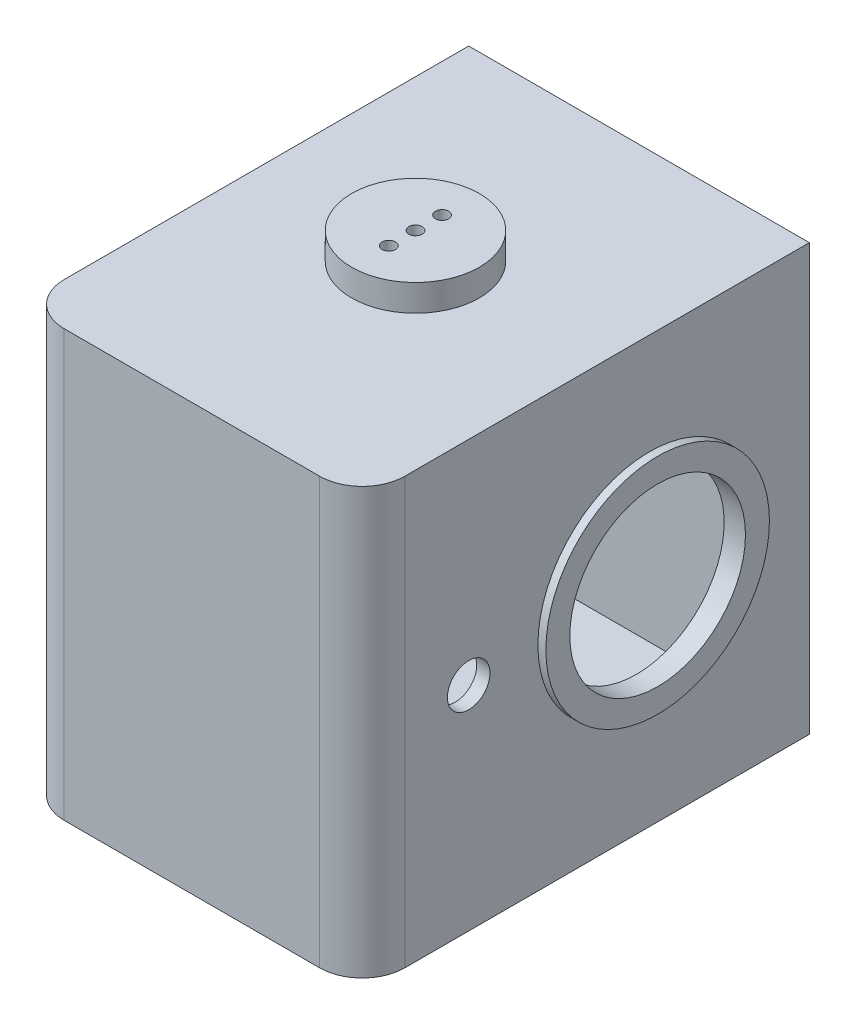
SolidWorks part; units mm, degrees
ref_plane "Front Plane" through (0, 0, 0) normal (0, 0, 1) x (1, 0, 0)
ref_plane "Top Plane" through (0, 0, 0) normal (0, 1, 0) x (1, 0, 0)
ref_plane "Right Plane" through (0, 0, 0) normal (1, 0, 0) x (0, 0, -1)
sketch "S_box1" plane through (0, 0, 0) normal (0, 0, 1) x (1, 0, 0)
  line L0 (-32, -40) -> (32, -40)
  line L1 (32, -40) -> (32, 40)
  line L2 (32, 40) -> (-32, 40)
  line L3 (-32, 40) -> (-32, -40)
  dimension "P1" = 32
  dimension "P2" = 40
  dimension "P3" = 32
  dimension "P4" = 40
  dimension "P5" = 32
  dimension "P6" = 40
  dimension "P7" = 32
  dimension "P8" = 40
extrude "Boss_1" add sketch "S_box1" along normal blind 76
ref_plane "PZ_p75_900" through (0, 0, 75.9) normal (0, 0, 1) x (1, 0, 0)
sketch "S_box2" plane through (0, 0, 75.9) normal (0, 0, 1) x (1, 0, 0)
  line L0 (-24, -40) -> (24, -40)
  line L1 (24, -40) -> (24, 40)
  line L2 (24, 40) -> (-24, 40)
  line L3 (-24, 40) -> (-24, -40)
  dimension "P1" = 24
  dimension "P2" = 40
  dimension "P3" = 24
  dimension "P4" = 40
  dimension "P5" = 24
  dimension "P6" = 40
  dimension "P7" = 24
  dimension "P8" = 40
extrude "Boss_2" add sketch "S_box2" along normal blind 8.1
ref_plane "PY_m40_000" through (0, -40, 0) normal (0, 1, 0) x (1, 0, 0)
sketch "S_cyl3" plane through (0, -40, 0) normal (0, 1, 0) x (1, 0, 0)
  circle A0 centre (-24, -76) radius 8
  dimension "D1_S_cyl3" = 16
  dimension "P2" = 24
  dimension "P3" = 76
extrude "Boss_3" add sketch "S_cyl3" along normal blind 80
sketch "S_cyl4" plane through (0, -40, 0) normal (0, 1, 0) x (1, 0, 0)
  circle A0 centre (24, -76) radius 8
  dimension "D1_S_cyl4" = 16
  dimension "P2" = 24
  dimension "P3" = 76
extrude "Boss_4" add sketch "S_cyl4" along normal blind 80
ref_plane "PX_p31_900" through (31.9, 0, 0) normal (1, 0, 0) x (0, 0, -1)
sketch "S_cyl5" plane through (31.9, 0, 0) normal (1, 0, 0) x (0, 0, -1)
  circle A0 centre (-30, 0) radius 21
  dimension "D1_S_cyl5" = 42
  dimension "P2" = 30
extrude "Boss_5" add sketch "S_cyl5" along normal blind 1.6
ref_plane "PY_p39_900" through (0, 39.9, 0) normal (0, 1, 0) x (1, 0, 0)
sketch "S_cyl6" plane through (0, 39.9, 0) normal (0, 1, 0) x (1, 0, 0)
  circle A0 centre (-2, -40) radius 12
  dimension "D1_S_cyl6" = 24
  dimension "P2" = 2
  dimension "P3" = 40
extrude "Boss_6" add sketch "S_cyl6" along normal blind 5.1
ref_plane "PY_m45_000" through (0, -45, 0) normal (0, 1, 0) x (1, 0, 0)
sketch "S_cyl7" plane through (0, -45, 0) normal (0, 1, 0) x (1, 0, 0)
  circle A0 centre (-2, -40) radius 12
  dimension "D1_S_cyl7" = 24
  dimension "P2" = 2
  dimension "P3" = 40
extrude "Boss_7" add sketch "S_cyl7" along normal blind 5.1
ref_plane "PZ_p2_500" through (0, 0, 2.5) normal (0, 0, 1) x (1, 0, 0)
sketch "S_cut8" plane through (0, 0, 2.5) normal (0, 0, 1) x (1, 0, 0)
  line L0 (-33, -37.5) -> (29.5, -37.5)
  line L1 (29.5, -37.5) -> (29.5, 37.5)
  line L2 (29.5, 37.5) -> (-33, 37.5)
  line L3 (-33, 37.5) -> (-33, -37.5)
  dimension "P1" = 33
  dimension "P2" = 37.5
  dimension "P3" = 29.5
  dimension "P4" = 37.5
  dimension "P5" = 29.5
  dimension "P6" = 37.5
  dimension "P7" = 33
  dimension "P8" = 37.5
extrude "Pocket_8" cut sketch "S_cut8" along normal blind 73.5
sketch "S_cut9" plane through (0, 0, 75.9) normal (0, 0, 1) x (1, 0, 0)
  line L0 (-24, -37.5) -> (24, -37.5)
  line L1 (24, -37.5) -> (24, 37.5)
  line L2 (24, 37.5) -> (-24, 37.5)
  line L3 (-24, 37.5) -> (-24, -37.5)
  dimension "P1" = 24
  dimension "P2" = 37.5
  dimension "P3" = 24
  dimension "P4" = 37.5
  dimension "P5" = 24
  dimension "P6" = 37.5
  dimension "P7" = 24
  dimension "P8" = 37.5
extrude "Pocket_9" cut sketch "S_cut9" along normal blind 5.6
ref_plane "PY_m37_500" through (0, -37.5, 0) normal (0, 1, 0) x (1, 0, 0)
sketch "S_hole10" plane through (0, -37.5, 0) normal (0, 1, 0) x (1, 0, 0)
  circle A0 centre (-24, -76) radius 5.5
  dimension "D1_S_hole10" = 11
  dimension "P2" = 24
  dimension "P3" = 76
extrude "Hole_10" cut sketch "S_hole10" along normal blind 75
sketch "S_hole11" plane through (0, -37.5, 0) normal (0, 1, 0) x (1, 0, 0)
  circle A0 centre (24, -76) radius 5.5
  dimension "D1_S_hole11" = 11
  dimension "P2" = 24
  dimension "P3" = 76
extrude "Hole_11" cut sketch "S_hole11" along normal blind 75
ref_plane "PX_p29_400" through (29.4, 0, 0) normal (1, 0, 0) x (0, 0, -1)
sketch "S_hole12" plane through (29.4, 0, 0) normal (1, 0, 0) x (0, 0, -1)
  circle A0 centre (-30, 0) radius 16.5
  dimension "D1_S_hole12" = 33
  dimension "P2" = 30
extrude "Hole_12" cut sketch "S_hole12" along normal blind 4.2
sketch "S_hole13" plane through (29.4, 0, 0) normal (1, 0, 0) x (0, 0, -1)
  circle A0 centre (-64, 0) radius 4
  dimension "D1_S_hole13" = 8
  dimension "P2" = 64
extrude "Hole_13" cut sketch "S_hole13" along normal blind 2.7
ref_plane "PZ_m0_100" through (0, 0, -0.1) normal (0, 0, 1) x (1, 0, 0)
sketch "S_hole14" plane through (0, 0, -0.1) normal (0, 0, 1) x (1, 0, 0)
  circle A0 centre (0, 0) radius 1.5
  dimension "D1_S_hole14" = 3
extrude "Hole_14" cut sketch "S_hole14" along normal blind 2.7
sketch "S_hole15" plane through (0, 0, -0.1) normal (0, 0, 1) x (1, 0, 0)
  circle A0 centre (0, 7) radius 0.8
  dimension "D1_S_hole15" = 1.6
  dimension "P2" = 7
extrude "Hole_15" cut sketch "S_hole15" along normal blind 2.7
sketch "S_hole16" plane through (0, 0, -0.1) normal (0, 0, 1) x (1, 0, 0)
  circle A0 centre (0, -7) radius 0.8
  dimension "D1_S_hole16" = 1.6
  dimension "P2" = 7
extrude "Hole_16" cut sketch "S_hole16" along normal blind 2.7
ref_plane "PY_p37_400" through (0, 37.4, 0) normal (0, 1, 0) x (1, 0, 0)
sketch "S_hole17" plane through (0, 37.4, 0) normal (0, 1, 0) x (1, 0, 0)
  circle A0 centre (-2, -35) radius 1.25
  dimension "D1_S_hole17" = 2.5
  dimension "P2" = 2
  dimension "P3" = 35
extrude "Hole_17" cut sketch "S_hole17" along normal blind 7.7
ref_plane "PY_m45_100" through (0, -45.1, 0) normal (0, 1, 0) x (1, 0, 0)
sketch "S_hole18" plane through (0, -45.1, 0) normal (0, 1, 0) x (1, 0, 0)
  circle A0 centre (-2, -35) radius 1.25
  dimension "D1_S_hole18" = 2.5
  dimension "P2" = 2
  dimension "P3" = 35
extrude "Hole_18" cut sketch "S_hole18" along normal blind 7.7
sketch "S_hole19" plane through (0, 37.4, 0) normal (0, 1, 0) x (1, 0, 0)
  circle A0 centre (-2, -40) radius 1.25
  dimension "D1_S_hole19" = 2.5
  dimension "P2" = 2
  dimension "P3" = 40
extrude "Hole_19" cut sketch "S_hole19" along normal blind 7.7
sketch "S_hole20" plane through (0, -45.1, 0) normal (0, 1, 0) x (1, 0, 0)
  circle A0 centre (-2, -40) radius 1.25
  dimension "D1_S_hole20" = 2.5
  dimension "P2" = 2
  dimension "P3" = 40
extrude "Hole_20" cut sketch "S_hole20" along normal blind 7.7
sketch "S_hole21" plane through (0, 37.4, 0) normal (0, 1, 0) x (1, 0, 0)
  circle A0 centre (-2, -45) radius 1.25
  dimension "D1_S_hole21" = 2.5
  dimension "P2" = 2
  dimension "P3" = 45
extrude "Hole_21" cut sketch "S_hole21" along normal blind 7.7
sketch "S_hole22" plane through (0, -45.1, 0) normal (0, 1, 0) x (1, 0, 0)
  circle A0 centre (-2, -45) radius 1.25
  dimension "D1_S_hole22" = 2.5
  dimension "P2" = 2
  dimension "P3" = 45
extrude "Hole_22" cut sketch "S_hole22" along normal blind 7.7
equation "\"plate_t\" = 3"
equation "\"clearance\" = 0.4"
